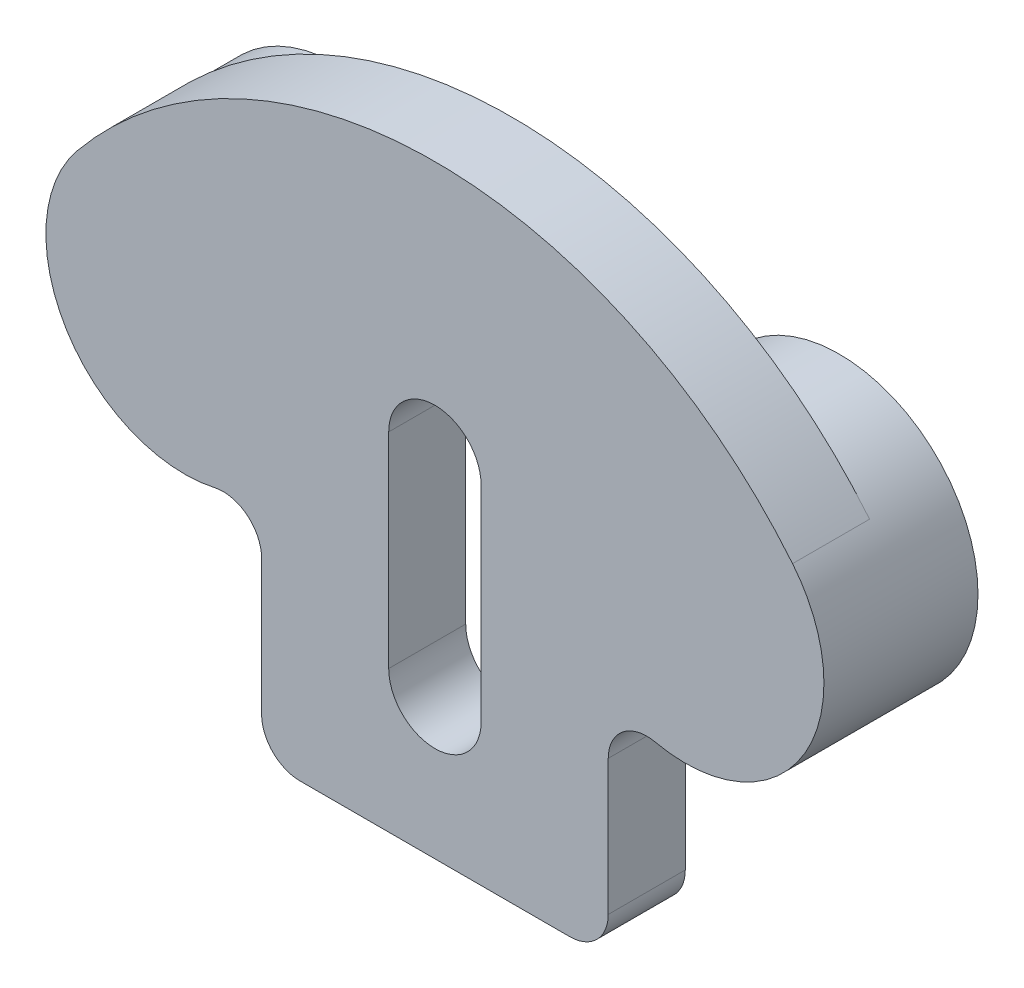
SolidWorks part; units mm, degrees
ref_plane "Front Plane" through (0, 0, 0) normal (0, 0, 1) x (1, 0, 0)
ref_plane "Top Plane" through (0, 0, 0) normal (0, 1, 0) x (1, 0, 0)
ref_plane "Right Plane" through (0, 0, 0) normal (1, 0, 0) x (0, 0, -1)
sketch "Sketch1" plane through (0, 0, 0) normal (0, 0, 1) x (1, 0, 0)
  line L0 (0, 78.5868) -> (0, -33.5202) construction
  line L1 (0, 0) -> (0, 26.6036) construction
  line L2 (-6, 0) -> (-6, 26.6036)
  line L3 (6, 0) -> (6, 26.6036)
  line L4 (-17.5, -18.3964) -> (17.5, -18.3964)
  line L5 (-77.9509, 26.6036) -> (87.6878, 26.6036) construction
  line L6 (-22.5, 4.1536) -> (-22.5, -13.3964)
  line L7 (22.5, 4.1536) -> (22.5, -13.3964)
  arc A1 (-6, 0) -> (6, 0) centre (0, 0) ccw
  arc A2 (6, 26.6036) -> (-6, 26.6036) centre (0, 26.6036) ccw
  arc A3 (46.4286, 38.0051) -> (-46.4286, 38.0051) centre (0, 0) ccw
  circle A4 centre (-32.5, 26.6036) radius 18
  circle A5 centre (-32.5, 26.6036) radius 13
  arc A6 (-28.587, 9.034) -> (-22.5, 4.1536) centre (-27.5, 4.1536) cw
  arc A7 (-22.5, -13.3964) -> (-17.5, -18.3964) centre (-17.5, -13.3964) ccw
  arc A8 (22.5, -13.3964) -> (17.5, -18.3964) centre (17.5, -13.3964) cw
  arc A9 (28.587, 9.034) -> (22.5, 4.1536) centre (27.5, 4.1536) ccw
  circle A10 centre (32.5, 26.6036) radius 13
  circle A11 centre (32.5, 26.6036) radius 18
  point P5 (0, 13.3018)
  point P10 (0, -18.3964)
  point P25 (-17.6468, -18.3964)
  point P27 (0, -18.3964)
  dimension "D1" = 6
  dimension "D3" = 36
  dimension "D4" = 26
  dimension "D6" = 120
  dimension "D7" = 5
  dimension "D8" = 5
  dimension "D2" = 45
  dimension "D5" = 32.5
  dimension "D9" = 22.5
extrude "Boss-Extrude1" add sketch "Sketch1" against normal blind 10 contours A9 A11 A3 A4 A6 L6 A7 L4 A8 L7 A2 L3 A1 L2 | A10 | A5 region at (-20.1762, -16.0726, 0) region at (-32.5, 26.6036, 0) region at (32.5, 26.6036, 0)
extrude "Boss-Extrude2" add sketch "Sketch1<3>" against normal blind 20 contours A11 A10 | A4 A5 region at (-47.3932, 17.4317, 0) region at (17.6068, 35.7754, 0)
sketch "Sketch1<3>" plane through (0, 0, 0) normal (0, 0, 1) x (1, 0, 0) same geometry as "Sketch1"
